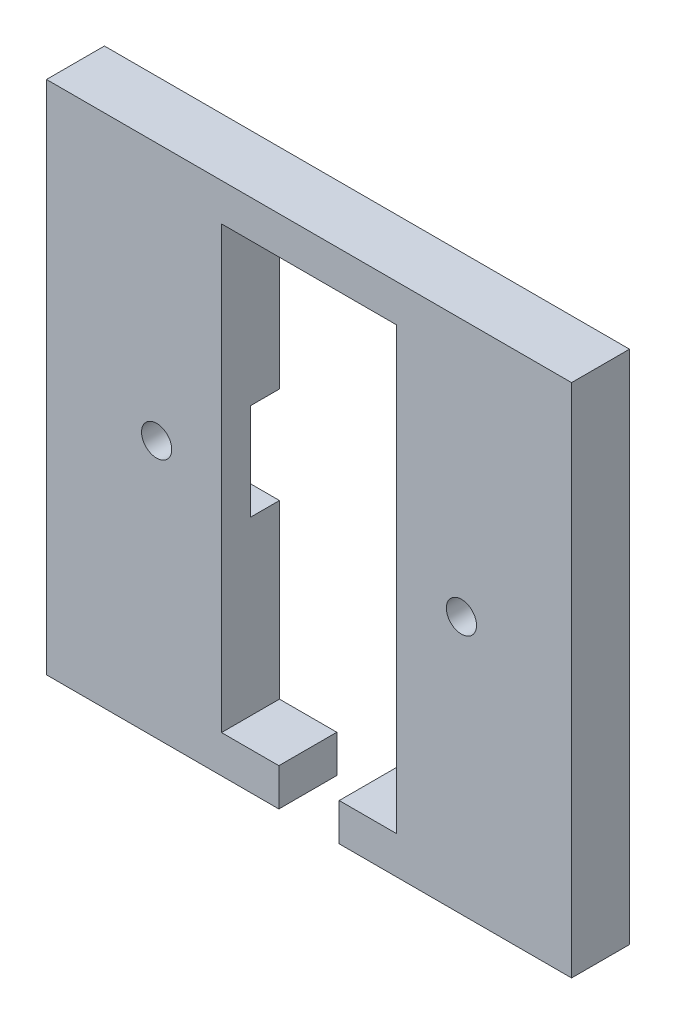
SolidWorks part; units mm, degrees
ref_plane "Front Plane" through (0, 0, 0) normal (0, 0, 1) x (1, 0, 0)
ref_plane "Top Plane" through (0, 0, 0) normal (0, 1, 0) x (1, 0, 0)
ref_plane "Right Plane" through (0, 0, 0) normal (1, 0, 0) x (0, 0, -1)
sketch "Sketch1" plane through (0, 0, 0) normal (0, 0, 1) x (1, 0, 0)
  line L0 (-7.25, 21.9766) -> (-7.25, -22.7855) construction
  line L1 (-19.25, 4) -> (-7.25, 4)
  line L2 (7.25, 4) -> (7.25, -4)
  line L3 (-7.25, 4) -> (-7.25, 18.25)
  line L5 (-21.75, 18.25) -> (-21.75, -18.25)
  line L6 (-13.25, 4) -> (-12.0009, -4) construction
  line L8 (-6.0009, 0) -> (-19.25, 0) construction
  line L11 (-19.25, -4) -> (-19.25, 4)
  line L12 (-19.25, 0) -> (-6.0009, 0)
  line L13 (-12.6254, 0) -> (12.6254, 0) construction
  line L14 (0, -18.25) -> (0, 18.25) construction
  line L15 (-7.25, 18.25) -> (7.25, 18.25)
  line L16 (7.25, 4) -> (7.25, 18.25)
  line L17 (-7.25, 4) -> (-7.25, -4)
  line L18 (21.75, 18.25) -> (21.75, -18.25)
  line L20 (19.25, 0) -> (6.0009, 0)
  line L21 (19.25, -4) -> (19.25, 4)
  line L22 (19.25, 4) -> (7.25, 4)
  line L23 (19.25, -4) -> (7.25, -4)
  line L25 (7.25, -4) -> (7.25, -18.25)
  line L26 (-7.25, -4) -> (-7.25, -18.25)
  line L27 (-7.25, -18.25) -> (7.25, -18.25)
  line L29 (-19.25, -4) -> (-7.25, -4)
  line L30 (-21.75, -21.3585) -> (21.75, -21.3585)
  line L32 (-21.75, 18.25) -> (-21.75, 21.3585)
  line L33 (-21.75, 21.3585) -> (21.75, 21.3585)
  line L34 (21.75, 18.25) -> (21.75, 21.3585)
  line L35 (21.75, -18.25) -> (21.75, -21.3585)
  line L37 (-21.75, -18.25) -> (-21.75, -21.3585)
  circle A0 centre (-12.6254, 0) radius 1.25
  circle A2 centre (12.6254, 0) radius 1.25
  point P20 (-12.6254, 0)
  point P25 (0, 0)
  dimension "D6" = 2.5
  dimension "D1" = 14.5
  dimension "D2" = 14.5
  dimension "D3" = 36.5
  dimension "D4" = 8
  dimension "D5" = 38.5
  dimension "D7" = 12.6254
  dimension "D8" = 43.5
  dimension "D9" = 42.7169
extrude "Boss-Extrude1" add sketch "Sketch1" along normal blind 4.8 contours L5 L37 L30 L35 L18 L34 L33 L32
extrude "Cut-Extrude1" cut sketch "Sketch1<12>" against normal through all both and the other way through all contours L26 L27 L25 L2 L16 L15 L3 L17 region at (0, 0, 0)
sketch "Sketch1<12>" plane through (0, 0, 0) normal (0, 0, 1) x (1, 0, 0) same geometry as "Sketch1"
extrude "Cut-Extrude2" cut sketch "Sketch1<13>" against normal through all both and the other way through all contours A0 | A2
sketch "Sketch1<13>" plane through (0, 0, 0) normal (0, 0, 1) x (1, 0, 0) same geometry as "Sketch1"
extrude "Cut-Extrude4" cut sketch "Sketch1<15>" along normal blind 2.4 contours A0 L12 L17 L1 L11 | A0 L12 L11 L29 L17 | L20 A2 L21 L22 L2 | L20 A2 L2 L23 L21 region at (-13.2837, 2.0792, 0) region at (-13.2837, -2.0792, 0) region at (13.2837, 2.0792, 0) region at (13.2837, -2.0792, 0)
sketch "Sketch1<15>" plane through (0, 0, 0) normal (0, 0, 1) x (1, 0, 0) same geometry as "Sketch1"
sketch "Sketch2" plane through (0, 0, 0) normal (0, 0, -1) x (-1, 0, 0)
  line L0 (-7.25, -18.25) -> (7.25, -18.25) construction
  line L1 (-2.5, -18.25) -> (2.5, -18.25)
  line L2 (-2.5, -18.25) -> (-2.5, -21.3585)
  line L3 (-2.5, -21.3585) -> (2.5, -21.3585)
  line L4 (2.5, -18.25) -> (2.5, -21.3585)
  line L5 (21.75, -21.3585) -> (-21.75, -21.3585) construction
  point P8 (0, -18.25)
  dimension "D1" = 5
extrude "Cut-Extrude5" cut sketch "Sketch2" against normal through all
